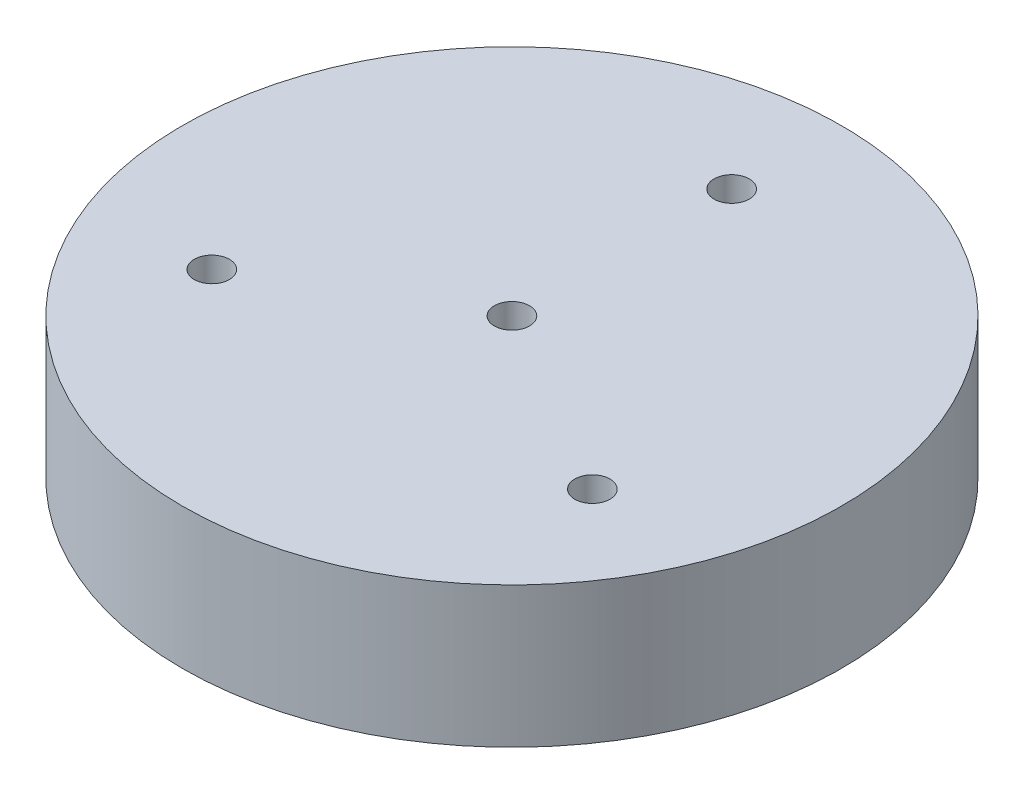
SolidWorks part; units mm, degrees
ref_plane "Ebene vorne" through (0, 0, 0) normal (0, 0, 1) x (1, 0, 0)
ref_plane "Ebene oben" through (0, 0, 0) normal (0, 1, 0) x (1, 0, 0)
ref_plane "Ebene rechts" through (0, 0, 0) normal (1, 0, 0) x (0, 0, -1)
sketch "Sketch1" plane through (0, 0, 0) normal (0, 1, 0) x (1, 0, 0)
  circle A0 centre (0, 0) radius 75
  dimension "D1" = 150
extrude "Boss-Extrude1" add sketch "Sketch1" along normal blind 32
sketch "Sketch2" plane through (0, 32, 0) normal (0, 1, 0) x (1, 0, 0)
  circle A0 centre (0, 50) radius 4
  dimension "D1" = 8
  dimension "D2" = 50
extrude "Cut-Extrude1" cut sketch "Sketch2" against normal through all contours A0
ref_axis "Axis1" through (0, 33.6, 0) along (0, -1, 0)
pattern_circular "CirPattern1" count 3 over 360 about axis through (0, 33.6, 0) along (0, -1, 0) of "Cut-Extrude1"
sketch "Sketch3" plane through (0, 32, 0) normal (0, 1, 0) x (1, 0, 0)
  circle A0 centre (0, 0) radius 4
  dimension "D1" = 8
extrude "Cut-Extrude2" cut sketch "Sketch3" against normal through all
equation "\"d_body\"= 150mm'diameter of composite body tube"
equation "\"t_body\"= 2mm'thickness of composite body tube"
equation "\"l_upper_body\"= 1150mm'axial length of upper body tube (RORO I)"
equation "\"D1@Sketch1\"=\"d_body\""
